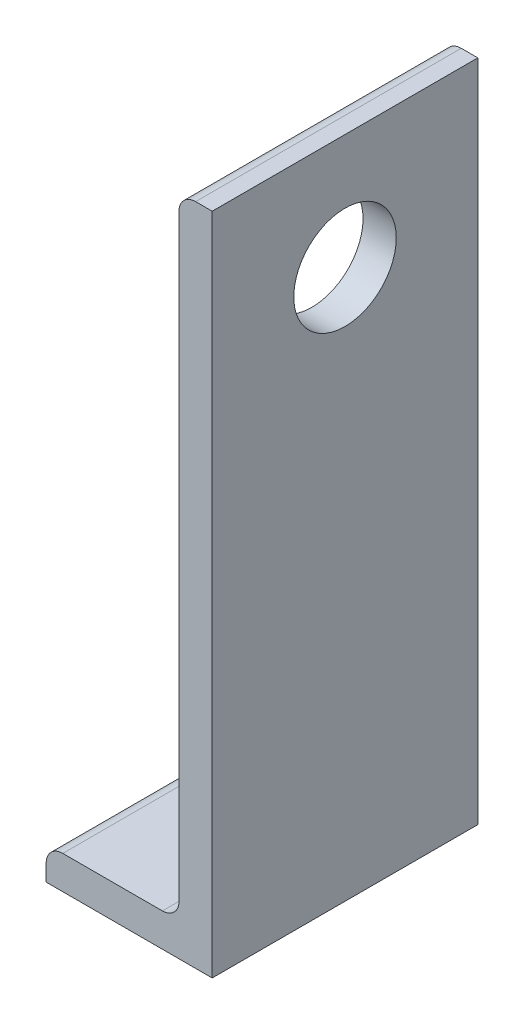
SolidWorks part; units mm, degrees
ref_plane "Front Plane" through (0, 0, 0) normal (0, 0, 1) x (1, 0, 0)
ref_plane "Top Plane" through (0, 0, 0) normal (0, 1, 0) x (1, 0, 0)
ref_plane "Right Plane" through (0, 0, 0) normal (1, 0, 0) x (0, 0, -1)
sketch "Sketch2" plane through (0, 0, 0) normal (0, 0, 1) x (1, 0, 0)
  line L0 (-15.875, 0) -> (15.875, 0)
  line L1 (15.875, 0) -> (15.875, 127)
  line L2 (15.875, 127) -> (9.525, 127) construction
  line L3 (9.525, 123.825) -> (9.525, 9.525)
  line L4 (6.35, 6.35) -> (-12.7, 6.35)
  line L5 (-15.875, 0) -> (-15.875, 6.35) construction
  line L6 (12.7, 127) -> (15.875, 127)
  line L7 (-15.875, 3.175) -> (-15.875, 0)
  arc A0 (9.525, 123.825) -> (12.7, 127) centre (12.7, 123.825) cw
  arc A1 (-15.875, 3.175) -> (-12.7, 6.35) centre (-12.7, 3.175) cw
  arc A2 (9.525, 9.525) -> (6.35, 6.35) centre (6.35, 9.525) cw
  dimension "Vert" = 127
  dimension "Horz" = 31.75
  dimension "Thickness" = 6.35
extrude "Boss-Extrude1" add sketch "Sketch2" along normal mid plane 50.8
ref_plane "Contact Plane 1" through (0, 6.35, 0) normal (0, 1, 0) x (1, 0, 0)
ref_plane "Contact Plane 2" through (9.525, 0, 0) normal (-1, 0, 0) x (0, 0, 1)
sketch "Sketch3" plane through (0, 0, 0) normal (0, -1, 0) x (1, 0, 0)
  line L0 (15.875, 0) -> (-15.875, 0) construction
  line L1 (15.875, 25.4) -> (15.875, -25.4) construction
  line L2 (-15.875, 25.4) -> (-15.875, -25.4) construction
  circle A0 centre (-4.826, 0) radius 4.765
  dimension "D1" = 9.53
  dimension "D2" = 20.701
extrude "Cut-Extrude1" cut sketch "Sketch3" against normal through all contours A0
sketch "Sketch5" plane through (15.875, 0, 0) normal (1, 0, 0) x (0, 0, -1)
  line L0 (-25.4, 0) -> (-25.4, 127) construction
  circle A0 centre (0, 105) radius 9.8
  dimension "D1" = 25.4
  dimension "D2" = 105
  dimension "D3" = 19.6
extrude "Cut-Extrude2" cut sketch "Sketch5" against normal blind 12.7
